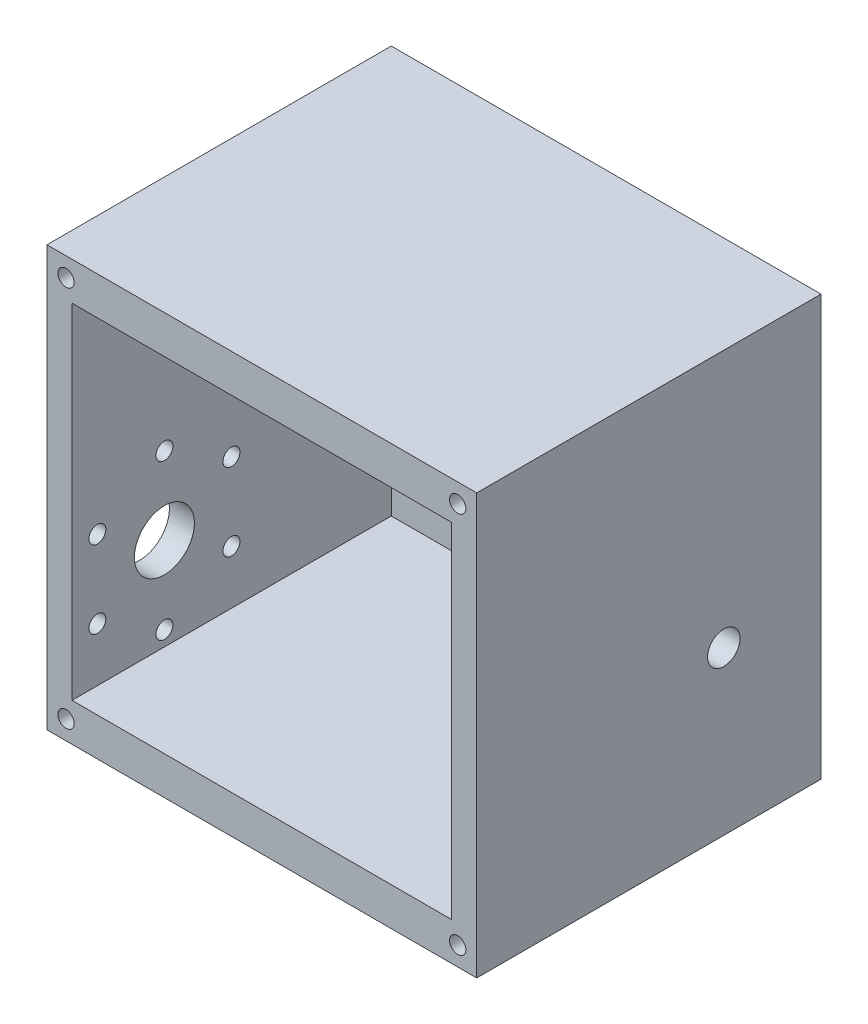
SolidWorks part; units mm, degrees
ref_plane "Front" through (0, 0, 0) normal (0, 0, 1) x (1, 0, 0)
ref_plane "Top" through (0, 0, 0) normal (0, 1, 0) x (1, 0, 0)
ref_plane "Right" through (0, 0, 0) normal (1, 0, 0) x (0, 0, -1)
sketch "Sketch1" plane through (0, 0, 0) normal (0, 0, 1) x (1, 0, 0)
  line L1 (-43, -42.037) -> (43, -42.037)
  line L2 (-43, -42.037) -> (-43, 42.037)
  line L3 (-43, 42.037) -> (43, 42.037)
  line L4 (43, -42.037) -> (43, 42.037)
  line L5 (-43, -42.037) -> (43, 42.037) construction
  line L6 (-43, 42.037) -> (43, -42.037) construction
  point P0 (0, 0)
  dimension "D1" = 86
  dimension "D2" = 84.074
extrude "Boss-Extrude1" add sketch "Sketch1" along normal blind 68.9031
sketch "Sketch2" plane through (0, 0, 68.9031) normal (0, 0, 1) x (1, 0, 0)
  line L0 (43, 42.037) -> (-43, 42.037) construction
  line L1 (-38, -34.417) -> (38, -34.417)
  line L2 (-38, -34.417) -> (-38, 34.417)
  line L3 (-38, 34.417) -> (38, 34.417)
  line L4 (38, -34.417) -> (38, 34.417)
  line L5 (-38, -34.417) -> (38, 34.417) construction
  line L6 (-38, 34.417) -> (38, -34.417) construction
  line L7 (-43, 42.037) -> (-43, -42.037) construction
  point P0 (0, 0)
  dimension "D1" = 7.62
  dimension "D2" = 5
extrude "Cut-Extrude1" cut sketch "Sketch2" against normal offset from surface (63.9031 mm away) 5 up to face at (0, 0, 0)
sketch "Sketch3" plane through (0, 0, 5) normal (0, 0, 1) x (1, 0, 0)
  line L0 (38, 34.417) -> (-38, 34.417) construction
  line L1 (-11.276, 34.417) -> (-3.656, 34.417)
  line L2 (-11.276, 34.417) -> (-11.276, 26.797)
  line L3 (-11.276, 26.797) -> (-3.656, 26.797)
  line L4 (-3.656, 34.417) -> (-3.656, 26.797)
  line L5 (30.38, 34.417) -> (38, 34.417)
  line L6 (30.38, 34.417) -> (30.38, 26.797)
  line L7 (30.38, 26.797) -> (38, 26.797)
  line L8 (38, 34.417) -> (38, 26.797)
  line L9 (-11.276, -14.097) -> (-3.656, -14.097)
  line L10 (-11.276, -14.097) -> (-11.276, -21.717)
  line L11 (-11.276, -21.717) -> (-3.656, -21.717)
  line L12 (-3.656, -14.097) -> (-3.656, -21.717)
  line L13 (30.38, -14.097) -> (38, -14.097)
  line L14 (30.38, -14.097) -> (30.38, -21.717)
  line L15 (30.38, -21.717) -> (38, -21.717)
  line L16 (38, -14.097) -> (38, -21.717)
  line L17 (38, -34.417) -> (38, 34.417) construction
  dimension "D1" = 7.62
  dimension "D2" = 49.276
  dimension "D3" = 56.134
extrude "Boss-Extrude2" add sketch "Sketch3" along normal blind 6.35
hole_wizard "#4-40 Tapped Hole1" positions "Sketch6" profile "Sketch7" tap size "#4-40" standard "ANSI Inch"
sketch "Sketch6" plane through (0, 0, 11.35) normal (0, 0, 1) x (1, 0, 0)
  line L1 (-3.656, 34.417) -> (-11.276, 34.417) construction
  line L2 (-11.276, 34.417) -> (-11.276, 26.797) construction
  line L3 (38, 34.417) -> (30.38, 34.417) construction
  line L4 (30.38, 34.417) -> (30.38, 26.797) construction
  line L5 (-3.656, -14.097) -> (-11.276, -14.097) construction
  line L6 (-11.276, -14.097) -> (-11.276, -21.717) construction
  line L7 (38, -14.097) -> (30.38, -14.097) construction
  line L8 (30.38, -14.097) -> (30.38, -21.717) construction
  point P0 (-7.466, 30.607)
  point P2 (34.19, 30.607)
  point P4 (-7.466, -17.907)
  point P6 (34.19, -17.907)
  point P16 (-7.466, 34.417)
  point P20 (-11.276, 30.607)
  point P24 (34.19, 34.417)
  point P28 (30.38, 30.607)
  point P32 (-7.466, -14.097)
  point P36 (-11.276, -17.907)
  point P40 (34.19, -14.097)
  point P44 (30.38, -17.907)
sketch "Sketch7" plane through (-7.466, 30.607, 11.35) normal (1, 0, 0) x (0, -1, 0)
  line L0 (0, 0) -> (0, 5.429)
  line L1 (0, 5.429) -> (1.1303, 4.7498)
  line L2 (1.1303, 4.7498) -> (1.1303, 0)
  line L5 (1.1303, 0) -> (0, 0)
  line L10 (0, 5.429) -> (-1.1303, 4.7498) construction
  line L11 (0, -6.35) -> (0, 107.95) construction
  dimension "Tap Drill Dia." = 2.2606
  dimension "Tap Drill Depth" = 4.7498
  dimension "Drill Angle" = 118
cosmetic thread "Hole Thread1" parameters "D1"=5.588, "D2"=2.8448
cosmetic thread "Hole Thread2" parameters "D1"=5.588, "D2"=2.8448
cosmetic thread "Hole Thread3" parameters "D1"=5.588, "D2"=2.8448
cosmetic thread "Hole Thread4" parameters "D1"=5.588, "D2"=2.8448
hole_wizard "Ø6.5 (6.5) Diameter Hole1" positions "Sketch8" profile "Sketch9" hole size "Ø6.5" standard "ANSI Metric" end condition up to next
sketch "Sketch8" plane through (43, 0, 0) normal (1, 0, 0) x (0, 0, -1)
  line L0 (-11.35, -21.717) -> (-5, -21.717) construction
  line L1 (-11.35, -21.717) -> (-11.35, -14.097) construction
  point P0 (-19.4502, -9.525)
  dimension "D1" = 12.192
  dimension "D2" = 8.1002
sketch "Sketch9" plane through (43, -9.525, 19.4502) normal (0, 1, 0) x (0, 0, -1)
  line L0 (0, 0) -> (0, 5)
  line L1 (0, 5) -> (3.25, 5)
  line L2 (3.25, 5) -> (3.25, 0)
  line L5 (3.25, 0) -> (0, 0)
  line L11 (0, -6.35) -> (0, 107.95) construction
  dimension "Thru Hole Dia." = 6.5
  dimension "Thru Hole Depth" = 5
sketch "Sketch10" plane through (-43, 0, 0) normal (-1, 0, 0) x (0, 0, 1)
  line L0 (5, -34.417) -> (68.9031, -34.417) construction
  line L1 (68.9031, 34.417) -> (68.9031, -34.417) construction
  point P0 (50.4031, -15.917)
  dimension "D1" = 18.5
  dimension "D2" = 18.5
hole_wizard "Ø12.0 (12) Diameter Hole1" positions "Sketch11" profile "Sketch12" hole size "Ø12.0" standard "ANSI Metric" end condition up to next
sketch "Sketch11" plane through (-43, 0, 0) normal (-1, 0, 0) x (0, 0, 1)
  point P0 (50.4031, -15.917)
sketch "Sketch12" plane through (-43, -15.917, 50.4031) normal (0, 1, 0) x (0, 0, 1)
  line L0 (0, 0) -> (0, 5)
  line L1 (0, 5) -> (6, 5)
  line L2 (6, 5) -> (6, 0)
  line L5 (6, 0) -> (0, 0)
  line L11 (0, -6.35) -> (0, 107.95) construction
  dimension "Thru Hole Dia." = 12
  dimension "Thru Hole Depth" = 5
hole_wizard "CSK for M3 Flat Head Machine Screw1" positions "Sketch13" profile "Sketch14" countersink size "M3" standard "ANSI Metric" end condition up to next
sketch "Sketch13" plane through (-43, 0, 0) normal (-1, 0, 0) x (0, 0, 1)
  line L0 (50.4031, -15.917) -> (50.4031, -0.417) construction
  point P0 (50.4031, -0.417)
  point P10 (63.8265, -8.167)
  point P11 (63.8265, -23.667)
  point P12 (50.4031, -31.417)
  point P13 (36.9797, -23.667)
  point P14 (36.9797, -8.167)
  dimension "D1" = 15.5
  dimension "D3" = 15.5
  dimension "D2" = 6
sketch "Sketch14" plane through (-43, -0.417, 50.4031) normal (0, 1, 0) x (0, 0, 1)
  line L0 (0, 0) -> (0, 5)
  line L1 (0, 5) -> (1.7, 5)
  line L2 (1.7, 5) -> (1.7, 1.45)
  line L3 (1.7, 1.45) -> (3.15, 0)
  line L5 (3.15, 0) -> (0, 0)
  line L6 (-1.7, 1.45) -> (-3.15, 0) construction
  line L11 (0, -6.35) -> (0, 107.95) construction
  dimension "Thru Hole Dia." = 3.4
  dimension "Thru Hole Depth" = 5
  dimension "Near C'Sink Dia." = 6.3
  dimension "Near C'Sink Angle" = 90
hole_wizard "#4 Clearance Hole1" positions "Sketch15" profile "Sketch16" hole size "#4" standard "ANSI Inch" end condition up to next
sketch "Sketch15" plane through (0, 0, 68.9031) normal (0, 0, 1) x (1, 0, 0)
  line L0 (43, 42.037) -> (-43, 42.037) construction
  line L1 (-43, 42.037) -> (-43, -42.037) construction
  line L2 (43, -42.037) -> (43, 42.037) construction
  line L3 (-43, -42.037) -> (43, -42.037) construction
  point P0 (-39.19, 38.227)
  point P2 (39.19, 38.227)
  point P4 (-39.19, -38.227)
  point P6 (39.19, -38.227)
  dimension "D1" = 3.81
  dimension "D2" = 3.81
  dimension "D3" = 3.81
  dimension "D4" = 3.81
sketch "Sketch16" plane through (-39.19, 38.227, 68.9031) normal (1, 0, 0) x (0, -1, 0)
  line L0 (0, 0) -> (0, 68.9031)
  line L1 (0, 68.9031) -> (1.6319, 68.9031)
  line L2 (1.6319, 68.9031) -> (1.6319, 0)
  line L5 (1.6319, 0) -> (0, 0)
  line L11 (0, -6.35) -> (0, 107.95) construction
  dimension "Thru Hole Dia." = 3.2639
  dimension "Thru Hole Depth" = 68.9031
equation "\"PCB Width\"= 1940mil"
equation "\"PCB Height\"= 2210mil"
equation "\"PCB Thickness\"= 63mil"
equation "\"Motor Body Front Diameter\"= 37mm"
equation "\"Motor Body Front Length\"= 30mm"
equation "\"Motor Bearing Length\"= 5mm"
equation "\"Motor Body Back Length\"= 33.3mm"
equation "\"Large PVC Fittings Wall Thickness\"= 15in / 64"
equation "\"Large PVC Pipe Outer Diameter\"= 3.5in"
equation "\"Box Width\"= 2 * \"Motor Bearing Length\" + \"Motor Body Front Length\" + \"Motor Body Back Length\" + 0.5in"
equation "\"Box Hole Center to Edge Distance\"= 150mil"
equation "\"Box Ceiling and Floor Thickness\"= 2 * \"Box Hole Center to Edge Distance\""
equation "\"Box Height\"= 2 * \"Box Ceiling and Floor Thickness\" + \"PCB Height\" + 0.5in"
equation "\"Box Back Depth\"= \"Large PVC Fittings Wall Thickness\" + \"Large PVC Pipe Outer Diameter\" / 2 + \"Motor Body Front Diameter\" / 2"
equation "\"D1@Sketch1\"=\"Box Width\""
equation "\"D2@Sketch1\"=\"Box Height\""
equation "\"D1@Boss-Extrude1\"=\"Box Back Depth\""
equation "\"D1@Sketch2\"=\"Box Ceiling and Floor Thickness\""
equation "\"D2@Sketch2\"=\"Motor Bearing Length\""
equation "\"D1@Cut-Extrude1\"=\"Motor Bearing Length\""
equation "\"PCB Mount Width\"= 2 * \"Box Hole Center to Edge Distance\""
equation "\"D1@Sketch3\"=\"PCB Mount Width\""
equation "\"D2@Sketch3\"=\"PCB Width\""
equation "\"D3@Sketch3\"=\"PCB Height\""
equation "\"Tap Drill Depth@Sketch7\"=0.25in - \"PCB Thickness\""
equation "\"D2@Sketch8\"=\"PCB Thickness\" + 6.5mm"
equation "\"Motor Body Front Radius\"= \"Motor Body Front Diameter\" / 2"
equation "\"D1@Sketch10\"=\"Motor Body Front Radius\""
equation "\"D2@Sketch10\"=\"Motor Body Front Radius\""
equation "\"Motor PCR\"= 31mm / 2"
equation "\"D1@Sketch13\"=\"Motor PCR\""
equation "\"D1@Sketch15\"=\"Box Hole Center to Edge Distance\""
equation "\"D2@Sketch15\"=\"Box Hole Center to Edge Distance\""
equation "\"D3@Sketch15\"=\"Box Hole Center to Edge Distance\""
equation "\"D4@Sketch15\"=\"Box Hole Center to Edge Distance\""
